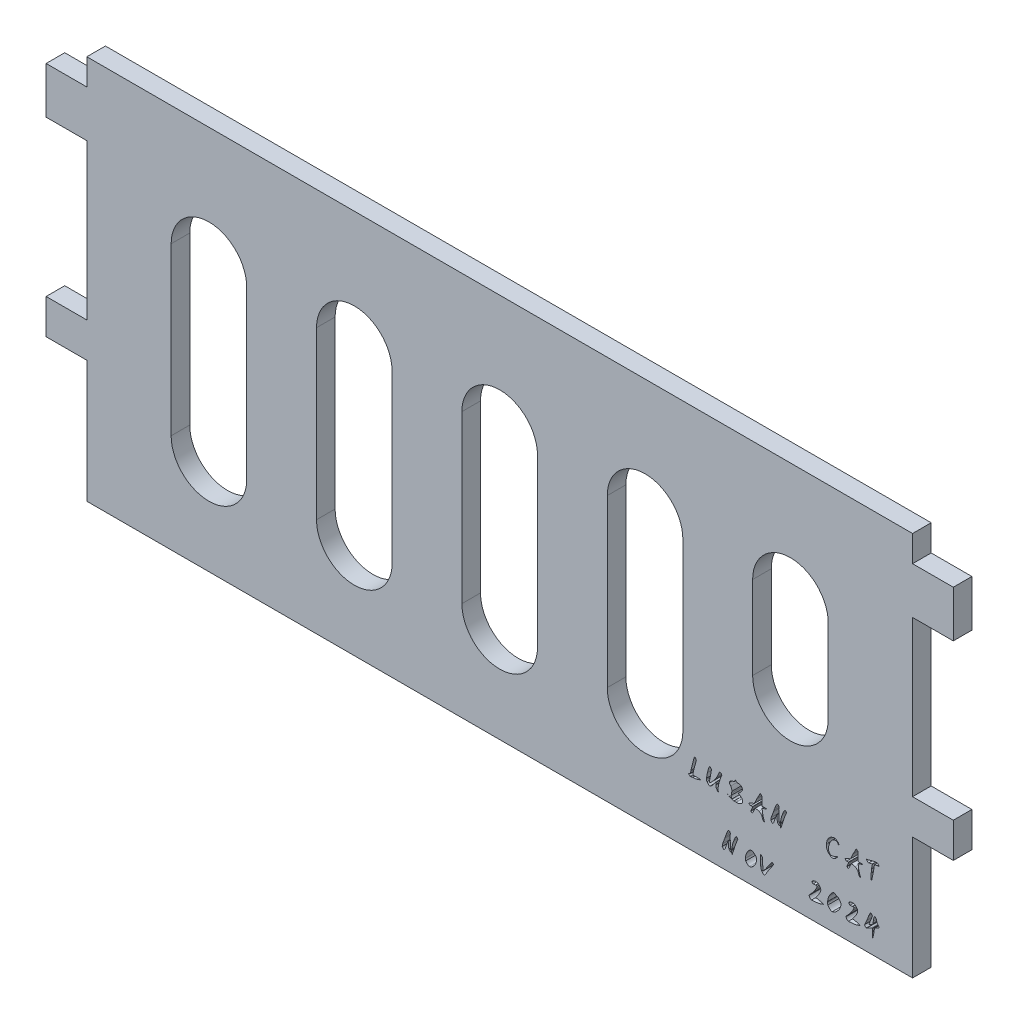
SolidWorks part; units mm, degrees
ref_plane "前视基准面" through (0, 0, 0) normal (0, 0, 1) x (1, 0, 0)
ref_plane "上视基准面" through (0, 0, 0) normal (0, 1, 0) x (1, 0, 0)
ref_plane "右视基准面" through (0, 0, 0) normal (1, 0, 0) x (0, 0, -1)
sketch "草图1" plane through (0, 0, 0) normal (0, 0, 1) x (1, 0, 0)
  line L0 (0, 0) -> (0, 38.8053) construction
  line L11 (0, 0) -> (-51.2518, 0) construction
  line L12 (39, 4) -> (-39, 4)
  line L13 (-39, 4) -> (-39, 0)
  line L14 (-39, 0) -> (-35.5, 0)
  line L15 (-35.5, 0) -> (-35.5, -16.35) construction
  line L16 (-35.5, -16.35) -> (35.5, -16.35)
  line L17 (35.5, 0) -> (35.5, -16.35) construction
  line L18 (39, 0) -> (35.5, 0)
  line L19 (39, 4) -> (39, 0)
  line L20 (-35.5, -13.35) -> (-39, -13.35)
  line L21 (-39, -13.35) -> (-39, -16.35)
  line L22 (-39, -16.35) -> (-35.5, -16.35)
  line L23 (-35.5, 0) -> (-35.5, -13.35)
  line L24 (39, -16.35) -> (35.5, -16.35)
  line L25 (39, -13.35) -> (39, -16.35)
  line L26 (35.5, -13.35) -> (39, -13.35)
  line L27 (35.5, 0) -> (35.5, -13.35)
  line L28 (-39, 2) -> (-43.2943, 2) construction
  point P6 (-37.25, 0)
  point P12 (0, -16.35)
  point P15 (0, 4)
  dimension "D1" = 3.5
  dimension "D2" = 4
  dimension "D3" = 71
  dimension "D4" = 15.35
  dimension "D5" = 3
extrude "主体" add sketch "草图1" along normal blind 1.6
ref_plane "旋转轴所在面" through (0, 0, 0.8) normal (0, 0, -1) x (-1, 0, 0)
sketch "旋转轴示意" plane through (0, 0, 0.8) normal (0, 0, -1) x (-1, 0, 0)
  line L0 (-39, 2) -> (-50.9061, 2) construction
  line L1 (-39, 0) -> (-39, 4) construction
sketch "草图3" plane through (0, 0, 0) normal (0, 0, -1) x (-1, 0, 0)
  line L0 (-35.5, 4) -> (-35.5, 6.25)
  line L1 (-39, 4) -> (39, 4) construction
  line L2 (-35.5, 6.25) -> (35.5, 6.25)
  line L3 (35.5, 6.25) -> (35.5, 4)
  line L4 (35.5, 4) -> (-35.5, 4)
  line L5 (-35.5, -13.35) -> (-35.5, 0) construction
  line L6 (35.5, 0) -> (35.5, -13.35) construction
  line L7 (-35.5, -26.85) -> (-35.5, -16.35)
  line L8 (-35.5, -16.35) -> (35.5, -16.35)
  line L9 (35.5, -16.35) -> (35.5, -26.85)
  line L10 (35.5, -26.85) -> (-35.5, -26.85)
  line L11 (39, -16.35) -> (-39, -16.35) construction
  dimension "D1" = 2.25
  dimension "D2" = 10.5
extrude "结构补强" add sketch "草图3" against normal up to surface (1.6 mm away) up to face at (0, -6.5083, 1.6)
sketch "草图4" plane through (0, 0, 1.6) normal (0, 0, 1) x (1, 0, 0)
  line L0 (0, -4.05) -> (0, -18.35) construction
  line L3 (3.25, -4.05) -> (3.25, -18.35)
  line L6 (-3.25, -4.05) -> (-3.25, -18.35)
  line L9 (-35.5, -26.85) -> (35.5, -26.85) construction
  line L12 (12.5, -4.05) -> (12.5, -18.35) construction
  line L13 (21.75, -4.05) -> (21.75, -11.2)
  line L14 (28.25, -4.05) -> (28.25, -11.2)
  line L15 (15.75, -4.05) -> (15.75, -18.35)
  line L16 (9.25, -4.05) -> (9.25, -18.35)
  line L17 (25, -4.05) -> (25, -18.35) construction
  line L18 (28.25, -4.05) -> (28.25, -18.35) construction
  line L19 (21.75, -4.05) -> (21.75, -18.35) construction
  line L20 (0, -4.05) -> (12.5, -4.05) construction
  line L21 (-12.5, -4.05) -> (-12.5, -18.35) construction
  line L22 (-9.25, -4.05) -> (-9.25, -18.35)
  line L23 (-15.75, -4.05) -> (-15.75, -18.35)
  line L24 (-25, -4.05) -> (-25, -18.35) construction
  line L25 (-21.75, -4.05) -> (-21.75, -18.35)
  line L26 (-28.25, -4.05) -> (-28.25, -18.35)
  line L27 (0, -4.05) -> (-12.5, -4.05) construction
  line L28 (35.5, -21.6) -> (15.75, -21.6) construction
  line L29 (35.5, -26.85) -> (35.5, -16.35) construction
  arc A8 (3.25, -4.05) -> (-3.25, -4.05) centre (0, -4.05) ccw
  arc A9 (-3.25, -18.35) -> (3.25, -18.35) centre (0, -18.35) ccw
  arc A10 (15.75, -4.05) -> (9.25, -4.05) centre (12.5, -4.05) ccw
  arc A11 (9.25, -18.35) -> (15.75, -18.35) centre (12.5, -18.35) ccw
  arc A12 (28.25, -4.05) -> (21.75, -4.05) centre (25, -4.05) ccw construction
  arc A13 (21.75, -18.35) -> (28.25, -18.35) centre (25, -18.35) ccw construction
  arc A14 (-9.25, -4.05) -> (-15.75, -4.05) centre (-12.5, -4.05) ccw
  arc A15 (-15.75, -18.35) -> (-9.25, -18.35) centre (-12.5, -18.35) ccw
  arc A16 (-21.75, -4.05) -> (-28.25, -4.05) centre (-25, -4.05) ccw
  arc A17 (-28.25, -18.35) -> (-21.75, -18.35) centre (-25, -18.35) ccw
  arc A18 (21.75, -11.2) -> (28.25, -11.2) centre (25, -11.2) ccw
  arc A19 (21.75, -4.05) -> (28.25, -4.05) centre (25, -4.05) cw
  text T0 "LUBAN CAT \r\nNov 2024 " font "演示夏行楷" height 1.5
  point P3 (0, -11.2)
  point P13 (12.5, -11.2)
  point P20 (25, -11.2)
  point P29 (-12.5, -11.2)
  point P37 (-25, -11.2)
  dimension "D3" = 3.25
  dimension "D2" = 8.5
  dimension "D4" = 12.5
  dimension "D1" = 4.05
  dimension "D5" = 12.5
  dimension "D6" = 3
extrude "切除-拉伸1" cut sketch "草图4" against normal through all
